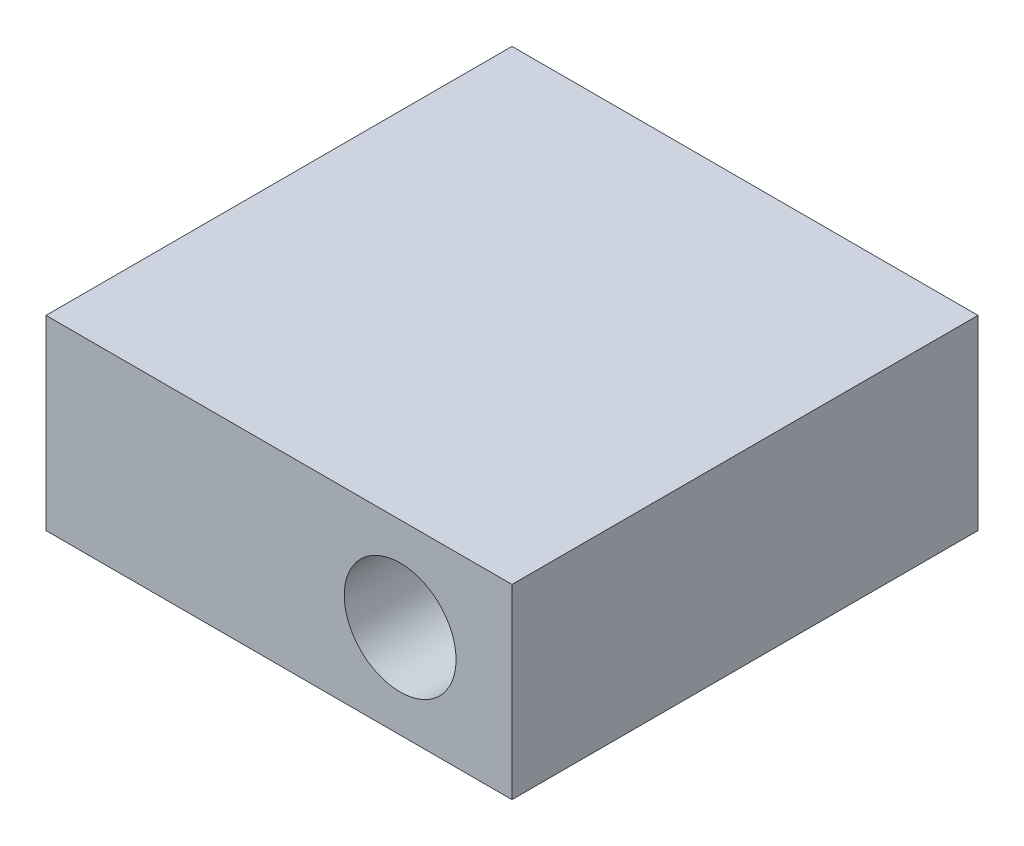
SolidWorks part; units mm, degrees
ref_plane "Front Plane" through (0, 0, 0) normal (0, 0, 1) x (1, 0, 0)
ref_plane "Top Plane" through (0, 0, 0) normal (0, 1, 0) x (1, 0, 0)
ref_plane "Right Plane" through (0, 0, 0) normal (1, 0, 0) x (0, 0, -1)
sketch "Sketch1" plane through (0, 0, 0) normal (0, 1, 0) x (1, 0, 0)
  line L1 (-12.5, -12.5) -> (12.5, -12.5)
  line L2 (-12.5, -12.5) -> (-12.5, 12.5)
  line L3 (-12.5, 12.5) -> (12.5, 12.5)
  line L4 (12.5, -12.5) -> (12.5, 12.5)
  line L5 (-12.5, -12.5) -> (12.5, 12.5) construction
  line L6 (-12.5, 12.5) -> (12.5, -12.5) construction
  point P0 (0, 0)
  dimension "D1" = 25
  dimension "D2" = 25
extrude "Boss-Extrude1" add sketch "Sketch1" along normal blind 10
sketch "Sketch2" plane through (0, 0, 12.5) normal (0, 0, 1) x (1, 0, 0)
  line L0 (12.5, 5) -> (6.5, 5) construction
  line L1 (12.5, 10) -> (12.5, 0) construction
  circle A0 centre (6.5, 5) radius 3
  dimension "D2" = 6
  dimension "D1" = 6
extrude "Cut-Extrude1" cut sketch "Sketch2" against normal blind 10
